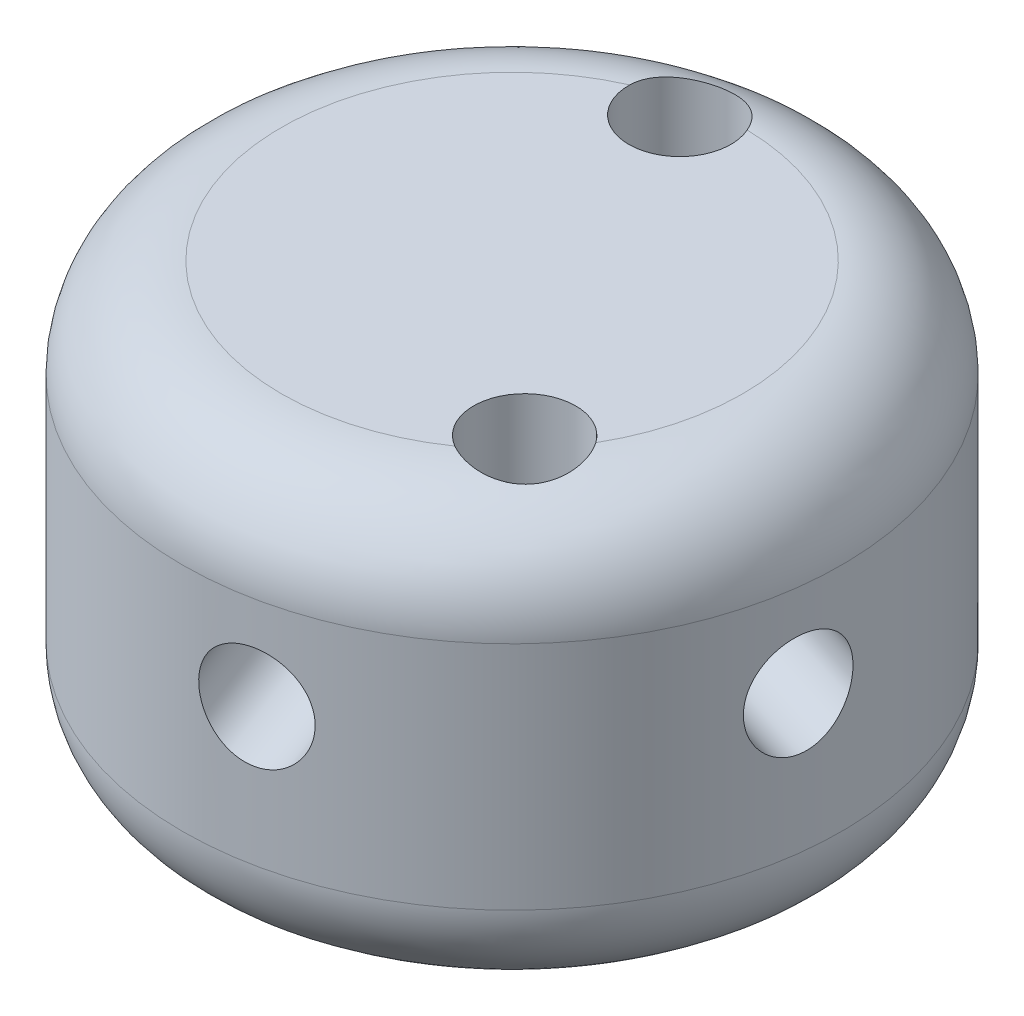
SolidWorks part; units mm, degrees
ref_plane "Front Plane" through (0, 0, 0) normal (0, 0, 1) x (1, 0, 0)
ref_plane "Top Plane" through (0, 0, 0) normal (0, 1, 0) x (1, 0, 0)
ref_plane "Right Plane" through (0, 0, 0) normal (1, 0, 0) x (0, 0, -1)
sketch "Sketch1" plane through (0, 0, 0) normal (0, 1, 0) x (1, 0, 0)
  circle A0 centre (0, 0) radius 10
  dimension "D1" = 20
extrude "Boss-Extrude1" add sketch "Sketch1" along normal blind 3 and the other way blind 10
ref_axis "5hubaxis" through (0, 5.5, 0) along (0, -1, 0)
ref_plane "holeplane" through (-3.3529, -1.0931, 1.8877) normal (0.8382, 0.2733, -0.4719) x (-0.4487, -0.1463, -0.8816)
sketch "Sketch4" plane through (-3.3529, -1.0931, 1.8877) normal (0.8382, 0.2733, -0.4719) x (-0.4487, -0.1463, -0.8816)
  circle A0 centre (0, 0) radius 1.5 construction
  circle A1 centre (0, 0) radius 1.5
extrude "hole" cut sketch "Sketch4" against normal through all
pattern_circular "holecir" count 5 over 360 about axis through (0, 5.5, 0) along (0, -1, 0) of "hole"
sketch "Sketch5" plane through (0, -10, 0) normal (0, -1, 0) x (1, 0, 0)
  line L0 (-10, 0) -> (10, 0) construction
  circle A0 centre (0, 0) radius 10 construction
  text T0 "5"
extrude "Boss-Extrude2" [suppressed] add sketch "Sketch5" along normal blind 1
ref_plane "Plane1" through (0, -5, 0) normal (0, -1, 0) x (-1, 0, 0)
sketch "Sketch6" plane through (0, -5, 0) normal (0, -1, 0) x (-1, 0, 0)
  circle A0 centre (0, 0) radius 3.5
  dimension "D1" = 7
extrude "bearinghole" cut sketch "Sketch6" along normal blind 2.5
sketch "Sketch7" plane through (0, -5, 0) normal (0, -1, 0) x (-1, 0, 0)
  circle A0 centre (0, 0) radius 2.05
  dimension "D1" = 4.1
extrude "shafthole" cut sketch "Sketch7" along normal through all
sketch "Sketch8" plane through (0, 3, 0) normal (0, 1, 0) x (1, 0, 0)
  line L0 (-1.9732, 9.8034) -> (0, 0) construction
  line L1 (0, 0) -> (7.3586, -6.7713) construction
  line L2 (0, 0) -> (1.9732, -9.8034) construction
  line L3 (3.4214, -9.3965) -> (2.2297, -3.4761) construction
  line L4 (0, 0) -> (9.9333, -1.1528) construction
  line L5 (9.9939, 0.3502) -> (3.995, 1.0464) construction
  line L6 (0, 0) -> (4.166, 9.0909) construction
  line L7 (2.7552, 9.613) -> (0.2393, 4.1229) construction
  circle A0 centre (0, 0) radius 10 construction
  circle A1 centre (0, 0) radius 6.5 construction
  point P15 (-1.2826, 6.3722)
  point P16 (4.7831, -4.4014)
  dimension "D3" = 13
  dimension "D1" = 36
  dimension "D2" = 36
hole_wizard "Ø3.1 (3.1) Diameter Hole1" positions "Sketch9" profile "Sketch10" hole size "Ø3.1" standard "ISO" end condition through all
sketch "Sketch9" plane through (0, 3, 0) normal (0, 1, 0) x (1, 0, 0)
  point P0 (-1.2826, 6.3722)
  point P3 (4.7831, -4.4014)
sketch "Sketch10" plane through (-1.2826, 3, -6.3722) normal (1, 0, 0) x (0, 0, 1)
  line L0 (0, 0) -> (0, 13)
  line L1 (0, 13) -> (1.55, 13)
  line L2 (1.55, 13) -> (1.55, 0)
  line L5 (1.55, 0) -> (0, 0)
  line L11 (0, -6.35) -> (0, 107.95) construction
  dimension "Thru Hole Dia." = 3.1
  dimension "Thru Hole Depth" = 13
fillet "Fillet2" radius 3 2 edges at (0, 3, 10) (0, -10, 10)
ref_plane "Plane2" through (0, -6.25, 0) normal (0, -1, 0) x (-1, 0, 0)
